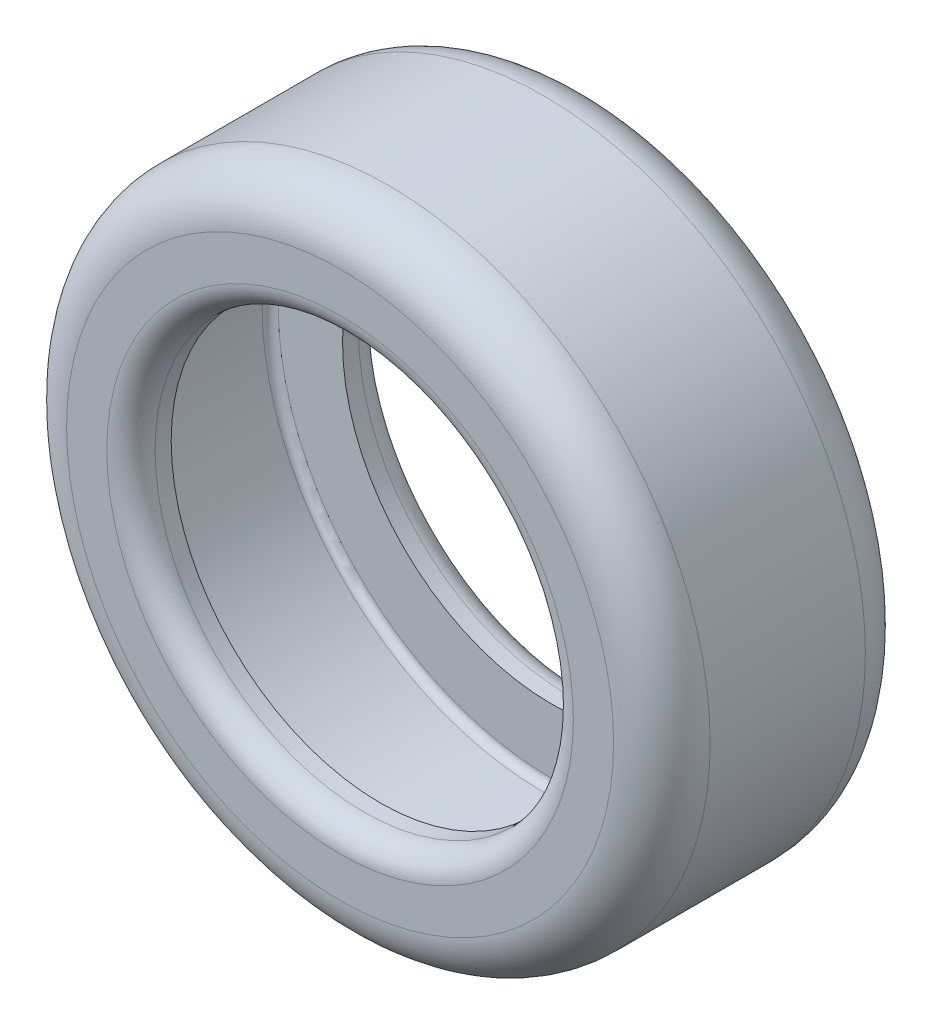
SolidWorks part; units mm, degrees
ref_plane "Front Plane" through (0, 0, 0) normal (0, 0, 1) x (1, 0, 0)
ref_plane "Top Plane" through (0, 0, 0) normal (0, 1, 0) x (1, 0, 0)
ref_plane "Right Plane" through (0, 0, 0) normal (1, 0, 0) x (0, 0, -1)
sketch "Sketch1" plane through (0, 0, 0) normal (0, 0, 1) x (1, 0, 0)
  circle A0 centre (0, 0) radius 101.6
  dimension "D1" = 203.2
extrude "Extrude-Thin1" add sketch "Sketch1" along normal blind 79.502 thin thin type one direction reverse wall 35.56
fillet "Fillet1" radius 15.24 2 edges at (101.6, 0, 0) (101.6, 0, 79.502)
fillet "Fillet2" radius 7.62 2 edges at (66.04, 0, 0) (66.04, 0, 79.502)
shell "Shell2" thickness 12.7 removed face at (66.04, 0, 7.62)
